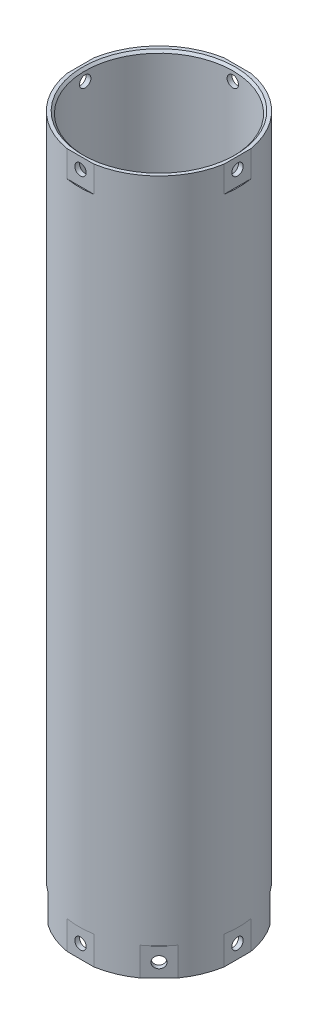
SolidWorks part; units mm, degrees
material "1060 Alloy"
ref_plane "Front Plane" through (0, 0, 0) normal (0, 0, 1) x (1, 0, 0)
ref_plane "Top Plane" through (0, 0, 0) normal (0, 1, 0) x (1, 0, 0)
ref_plane "Right Plane" through (0, 0, 0) normal (1, 0, 0) x (0, 0, -1)
sketch "Sketch2" plane through (0, 0, 0) normal (0, 0, 1) x (1, 0, 0)
  line L0 (0, 0) -> (0, 365.76) construction
  line L3 (41.275, 0) -> (44.45, 0)
  line L5 (41.275, 387.858) -> (44.45, 387.858)
  line L6 (44.45, 0) -> (44.45, 387.858)
  line L11 (41.275, 387.858) -> (41.275, 193.929)
  line L12 (41.275, 193.929) -> (41.2565, 193.9033)
  line L13 (41.275, 193.929) -> (41.275, 0)
  line L14 (0, -55) -> (0, 55) construction
  dimension "D3" = 3.175
  dimension "D4" = 387.858
revolve "Revolve1" add sketch "Sketch2" angle 360 about L0 region at (42.8625, 193.929, 0)
ref_axis "Axis1" through (0, -17.0472, 0) along (0, 1, 0)
ref_plane "Plane1" through (0, 7.62, 0) normal (0, -1, 0) x (-1, 0, 0)
ref_axis "Axis2" through (0, 7.62, 88.99) along (0, 0, -1)
hole_wizard "1/4 (0.25) Diameter Hole1" positions "3DSketch1" profile "Sketch3" hole size "1/4" standard "ANSI Inch" end condition up to next
sketch3d "3DSketch1"
  line L0 (0, 7.62, 88.99) -> (0, 7.62, -88.99) construction
  point P0 (0, 7.62, -44.45)
sketch "Sketch3" plane through (0, 7.62, -44.45) normal (1, 0, 0) x (0, 1, 0)
  line L0 (0, 0) -> (0, 3.175)
  line L1 (0, 3.175) -> (3.175, 3.175)
  line L2 (3.175, 3.175) -> (3.175, 0)
  line L5 (3.175, 0) -> (0, 0)
  line L11 (0, -6.35) -> (0, 107.95) construction
  dimension "Thru Hole Dia." = 6.35
  dimension "Thru Hole Depth" = 3.175
ref_plane "Plane2" through (0, 381.508, 0) normal (0, 1, 0) x (1, 0, 0)
ref_axis "Axis3" through (0, 381.508, -48.895) along (0, 0, 1)
sketch "Sketch4" plane through (0, 0, 0) normal (0, 0, 1) x (1, 0, 0)
  line L0 (0, -17.0472) -> (0, 357.9914) construction
  line L1 (0, 381.508) -> (-43.7642, 381.508)
  line L2 (0, 381.508) -> (0, 378.46)
  line L3 (0, 378.46) -> (-43.7642, 378.46)
  line L4 (-43.7642, 381.508) -> (-43.7642, 378.46)
  line L5 (48.895, 381.508) -> (-48.895, 381.508) construction
  dimension "D1" = 43.7642
  dimension "D2" = 3.048
revolve "Cut-Revolve2" [suppressed] cut sketch "Sketch4" angle 360 about axis through (0, -17.0472, 0) along (0, 1, 0)
hole_wizard "1/4 (0.25) Diameter Hole2" positions "3DSketch3" profile "Sketch6" hole size "1/4" standard "ANSI Inch"
sketch3d "3DSketch3"
  line L0 (0, 381.508, -48.895) -> (0, 381.508, 48.895) construction
  point P0 (0, 381.508, -44.45)
sketch "Sketch6" plane through (0, 381.508, -44.45) normal (1, 0, 0) x (0, 1, 0)
  line L0 (0, 0) -> (0, 5.2097)
  line L1 (0, 5.2097) -> (3.175, 3.302)
  line L2 (3.175, 3.302) -> (3.175, 0)
  line L5 (3.175, 0) -> (0, 0)
  line L10 (0, 5.2097) -> (-3.175, 3.302) construction
  line L11 (0, -6.35) -> (0, 107.95) construction
  dimension "Hole Dia." = 6.35
  dimension "Hole Depth" = 3.302
  dimension "Drill Angle" = 118
pattern_circular "CirPattern2" count 4 over 360 about axis through (0, -17.0472, 0) along (0, 1, 0) of "1/4 (0.25) Diameter Hole2" reverse direction yes
chamfer "Chamfer1" distance 1.27 angle 45 2 edges at (0, 0, -41.275) (0, 387.858, -41.275)
ref_plane "Plane3" through (44.45, 0, 0) normal (1, 0, 0) x (0, 0, -1)
pattern_circular "CirPattern1" count 8 over 360 about axis through (0, -17.0472, 0) along (0, 1, 0) of "1/4 (0.25) Diameter Hole1"
sketch "Sketch7" plane through (44.45, 0, 0) normal (1, 0, 0) x (0, 0, -1)
  line L1 (8.255, -0.635) -> (-8.255, -0.635)
  line L2 (8.255, -0.635) -> (8.255, 15.875)
  line L3 (8.255, 15.875) -> (-8.255, 15.875)
  line L4 (-8.255, -0.635) -> (-8.255, 15.875)
  circle A0 centre (0, 7.62) radius 3.175 construction
  dimension "D1" = 8.255
  dimension "D2" = 8.255
  dimension "D4" = 8.255
  dimension "D3" = 8.255
extrude "Cut-Extrude1" cut sketch "Sketch7" against normal blind 0.635
sketch "Sketch8" plane through (44.45, 0, 0) normal (1, 0, 0) x (0, 0, -1)
  line L1 (8.255, 373.253) -> (-8.255, 373.253)
  line L2 (8.255, 373.253) -> (8.255, 389.763)
  line L3 (8.255, 389.763) -> (-8.255, 389.763)
  line L4 (-8.255, 373.253) -> (-8.255, 389.763)
  circle A0 centre (0, 381.508) radius 3.175 construction
  dimension "D1" = 8.255
  dimension "D2" = 8.255
  dimension "D3" = 8.255
  dimension "D4" = 8.255
extrude "Cut-Extrude2" cut sketch "Sketch8" against normal blind 0.635
pattern_circular "CirPattern4" count 8 over 360 about axis through (0, -17.0472, 0) along (0, 1, 0) of "Cut-Extrude1"
pattern_circular "CirPattern5" count 4 over 360 about axis through (0, -17.0472, 0) along (0, 1, 0) of "Cut-Extrude2"
